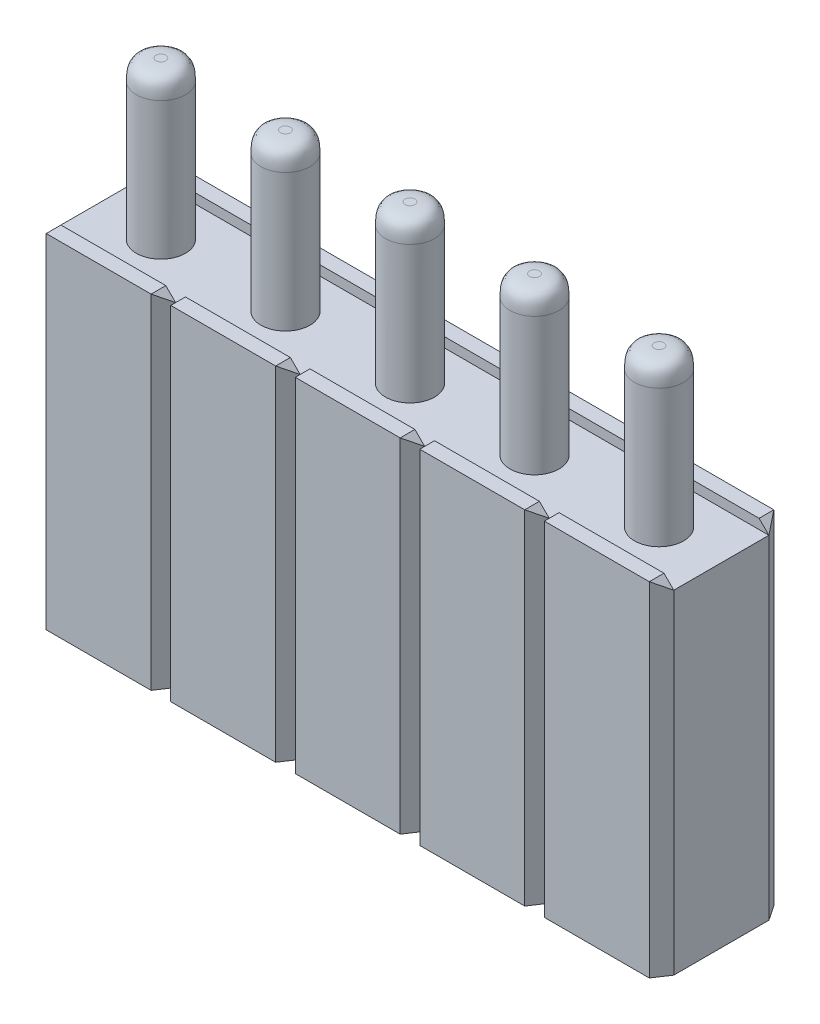
SolidWorks part; units mm, degrees
ref_plane "Plan de face" through (0, 0, 0) normal (0, 0, 1) x (1, 0, 0)
ref_plane "Plan de dessus" through (0, 0, 0) normal (0, 1, 0) x (1, 0, 0)
ref_plane "Plan de droite" through (0, 0, 0) normal (1, 0, 0) x (0, 0, -1)
sketch "Esquisse1" plane through (0, 0, 0) normal (1, 0, 0) x (0, 0, -1)
  line L0 (-0.97, 3.9901) -> (-0.97, -6.8373) construction
  line L1 (-1.27, -3.5) -> (1.27, -3.5)
  line L2 (-1.27, -3.5) -> (-1.27, 3.5)
  line L3 (-1.27, 3.5) -> (-0.97, 3.5)
  line L4 (1.27, -3.5) -> (1.27, 3.5)
  line L5 (-1.27, -3.5) -> (1.27, 3.5) construction
  line L6 (-1.27, 3.5) -> (1.27, -3.5) construction
  line L7 (-0.97, -6.8373) -> (0.97, -6.4139) construction
  line L8 (0.97, -6.4139) -> (0.97, 5.6016) construction
  line L9 (-0.97, 3.3) -> (0.97, 3.3)
  line L10 (0.97, 3.3) -> (0.97, 3.5)
  line L12 (-0.97, 3.5) -> (-0.97, 3.3)
  line L13 (0.97, 3.5) -> (1.27, 3.5)
  point P0 (0, 0)
  dimension "D1" = 2.54
  dimension "D2" = 7
  dimension "D3" = 0.3
  dimension "D4" = 0.3
  dimension "D5" = 0.2
extrude "Boss.-Extru.1" add sketch "Esquisse1" along normal blind 12.7
sketch "Esquisse2" plane through (0, 0, 1.27) normal (0, 0, 1) x (1, 0, 0)
  line L0 (2.54, 3.7737) -> (2.54, -3.7556) construction
  line L1 (2.54, -3.7556) -> (10.16, -3.7556) construction
  line L2 (10.16, -3.7556) -> (10.16, 3.7737) construction
  line L3 (0, 3.5) -> (0, -3.5) construction
  line L4 (12.7, 3.5) -> (12.7, -3.5) construction
  line L5 (0, 3.3) -> (0.2, 3.5)
  line L6 (12.7, 3.5) -> (0, 3.5) construction
  line L7 (2.54, 3.3) -> (2.34, 3.5)
  line L8 (12.7, 3.3) -> (0, 3.3) construction
  line L9 (2.54, 3.3) -> (2.74, 3.5)
  line L10 (10.16, 3.3) -> (9.96, 3.5)
  line L11 (10.16, 3.3) -> (10.36, 3.5)
  line L12 (12.7, 3.3) -> (12.5, 3.5)
  line L13 (0, 3.3) -> (-0.5087, 3.5467)
  line L14 (-0.5087, 3.5467) -> (-0.0607, 3.8227)
  line L15 (-0.0607, 3.8227) -> (0.563, 3.6847)
  line L16 (5.08, 3.3) -> (4.88, 3.5)
  line L17 (5.08, 3.3) -> (5.28, 3.5)
  line L18 (5.0103, 3.6847) -> (4.88, 3.5)
  line L19 (2.4703, 3.6847) -> (2.74, 3.6847)
  line L20 (5.28, 3.6847) -> (5.28, 3.5)
  line L21 (7.62, 3.3) -> (7.42, 3.5)
  line L22 (5.0103, 3.6847) -> (5.28, 3.6847)
  line L23 (7.62, 3.3) -> (7.82, 3.5)
  line L24 (2.74, 3.6847) -> (2.74, 3.5)
  line L25 (2.4703, 3.6847) -> (2.34, 3.5)
  line L26 (7.5503, 3.6847) -> (7.82, 3.6847)
  line L27 (12.6303, 3.6847) -> (12.9, 3.6847)
  line L28 (0.563, 3.6847) -> (0.2, 3.5)
  line L29 (7.5503, 3.6847) -> (7.42, 3.5)
  line L30 (7.82, 3.6847) -> (7.82, 3.5)
  line L31 (10.16, 3.3) -> (9.96, 3.5)
  line L32 (10.16, 3.3) -> (10.36, 3.5)
  line L33 (10.0903, 3.6847) -> (9.96, 3.5)
  line L34 (10.36, 3.6847) -> (10.36, 3.5)
  line L35 (12.7, 3.3) -> (12.5, 3.5)
  line L36 (12.7, 3.3) -> (12.9, 3.5)
  line L37 (12.6303, 3.6847) -> (12.5, 3.5)
  line L38 (12.9, 3.6847) -> (12.9, 3.5)
  line L39 (10.0903, 3.6847) -> (10.36, 3.6847)
  line M1 (0, 3.5) -> (0, -3.5)
  line M3 (12.7, -3.5) -> (12.7, 3.5)
  line M4 (12.7, 3.5) -> (0, 3.5)
  dimension "D1" = 2.54
  dimension "D2" = 2.54
  dimension "D3" = 5
extrude "Enlèv. mat.-Extru.1" cut sketch "Esquisse2" against normal through all contours L12 M3 M4 | L10 L11 M4 | L21 L23 M4 | L7 L9 M4 | L16 L17 M4 | L5 M1 M4
sketch "Esquisse3" plane through (0, -3.5, 0) normal (0, -1, 0) x (1, 0, 0)
  line L0 (0, 0.97) -> (0.2, 1.27)
  line L2 (2.34, 1.27) -> (2.54, 0.97)
  line L3 (2.54, 0.97) -> (2.74, 1.27)
  line L4 (0.2, 1.27) -> (0.2, 1.7272)
  line L5 (0.2, 1.7272) -> (-0.45, 1.27)
  line L6 (-0.45, -1.27) -> (-0.125, -1.5616)
  line L7 (-0.125, -1.5616) -> (0.2, -1.27)
  line L8 (2.34, -1.27) -> (2.54, -1.4929)
  line L10 (12.7, 1.27) -> (12.7, -1.27) construction
  line L11 (2.54, -1.4929) -> (2.74, -1.27)
  line L12 (2.34, 1.27) -> (2.5564, 1.5945)
  line L13 (2.5564, 1.5945) -> (2.74, 1.27)
  line L14 (5.08, 0.97) -> (5.28, 1.27)
  line L15 (-0.45, 1.27) -> (-0.3553, 1.1906)
  line L16 (-0.3553, 1.1906) -> (0, 0.97)
  line L17 (0, 0) -> (12.7, 0) construction
  line L18 (-0.45, -1.27) -> (-0.3553, -1.1906)
  line L19 (-0.3553, -1.1906) -> (0, -0.97)
  line L20 (0, -0.97) -> (0.2, -1.27)
  line L22 (2.34, -1.27) -> (2.54, -0.97)
  line L23 (2.54, -0.97) -> (2.74, -1.27)
  line L24 (4.88, 1.27) -> (5.08, 0.97)
  line L25 (4.88, 1.27) -> (5.0964, 1.5945)
  line L26 (5.0964, 1.5945) -> (5.28, 1.27)
  line L27 (5.08, -1.4929) -> (5.28, -1.27)
  line L28 (5.08, -0.97) -> (5.28, -1.27)
  line L29 (4.88, -1.27) -> (5.08, -0.97)
  line L30 (4.88, -1.27) -> (5.08, -1.4929)
  line L31 (7.62, 0.97) -> (7.82, 1.27)
  line L32 (7.42, 1.27) -> (7.62, 0.97)
  line L33 (7.42, 1.27) -> (7.6364, 1.5945)
  line L34 (7.6364, 1.5945) -> (7.82, 1.27)
  line L35 (7.62, -1.4929) -> (7.82, -1.27)
  line L36 (7.62, -0.97) -> (7.82, -1.27)
  line L37 (7.42, -1.27) -> (7.62, -0.97)
  line L38 (7.42, -1.27) -> (7.62, -1.4929)
  line L39 (10.16, 0.97) -> (10.36, 1.27)
  line L40 (9.96, 1.27) -> (10.16, 0.97)
  line L41 (9.96, 1.27) -> (10.1764, 1.5945)
  line L42 (10.1764, 1.5945) -> (10.36, 1.27)
  line L43 (10.16, -1.4929) -> (10.36, -1.27)
  line L44 (10.16, -0.97) -> (10.36, -1.27)
  line L45 (9.96, -1.27) -> (10.16, -0.97)
  line L46 (9.96, -1.27) -> (10.16, -1.4929)
  line L47 (12.7, 0.97) -> (12.9, 1.27)
  line L48 (12.5, 1.27) -> (12.7, 0.97)
  line L49 (12.5, 1.27) -> (12.7164, 1.5945)
  line L50 (12.7164, 1.5945) -> (12.9, 1.27)
  line L51 (12.7, -1.4929) -> (12.9, -1.27)
  line L52 (12.7, -0.97) -> (12.9, -1.27)
  line L53 (12.5, -1.27) -> (12.7, -0.97)
  line L54 (12.5, -1.27) -> (12.7, -1.4929)
  dimension "D1" = 5
extrude "Enlèv. mat.-Extru.2" cut sketch "Esquisse3" against normal through all
sketch "Esquisse4" plane through (0, -3.5, 0) normal (0, -1, 0) x (1, 0, 0)
  line L0 (0, 0) -> (12.7, 0) construction
  line L1 (0, 0.97) -> (0, -0.97) construction
  line L2 (12.7, 0.97) -> (12.7, -0.97) construction
  circle A0 centre (1.27, 0) radius 0.51
  circle A1 centre (3.81, 0) radius 0.51
  circle A2 centre (6.35, 0) radius 0.51
  circle A3 centre (8.89, 0) radius 0.51
  circle A4 centre (11.43, 0) radius 0.51
  dimension "D1" = 1.02
  dimension "D2" = 1.27
  dimension "D3" = 3
  dimension "D4" = 3
extrude "Enlèv. mat.-Extru.3" cut sketch "Esquisse4" against normal blind 6
chamfer "Chanfrein1" distance 0.1 angle 45 5 edges at (6.35, -3.5, -0.51) (3.81, -3.5, -0.51) (1.27, -3.5, -0.51) (11.43, -3.5, -0.51) (8.89, -3.5, -0.51)
sketch "Esquisse5" plane through (0, 3.3, 0) normal (0, 1, 0) x (1, 0, 0)
  line L0 (0, 0) -> (12.7, 0) construction
  line L1 (12.7, 0.97) -> (12.7, -0.97) construction
  line L2 (0, 0.97) -> (0, -0.97) construction
  circle A0 centre (1.27, 0) radius 0.5
  circle A1 centre (3.81, 0) radius 0.5
  circle A2 centre (6.35, 0) radius 0.5
  circle A3 centre (8.89, 0) radius 0.5
  circle A4 centre (11.43, 0) radius 0.5
  dimension "D1" = 1
  dimension "D2" = 1.27
  dimension "D3" = 3
  dimension "D4" = 3
extrude "Boss.-Extru.2" add sketch "Esquisse5" along normal blind 3.2
fillet "Congé1" radius 0.4 5 edges at (1.27, 6.5, 0.5) (6.35, 6.5, 0.5) (3.81, 6.5, 0.5) (11.43, 6.5, 0.5) (8.89, 6.5, 0.5)
